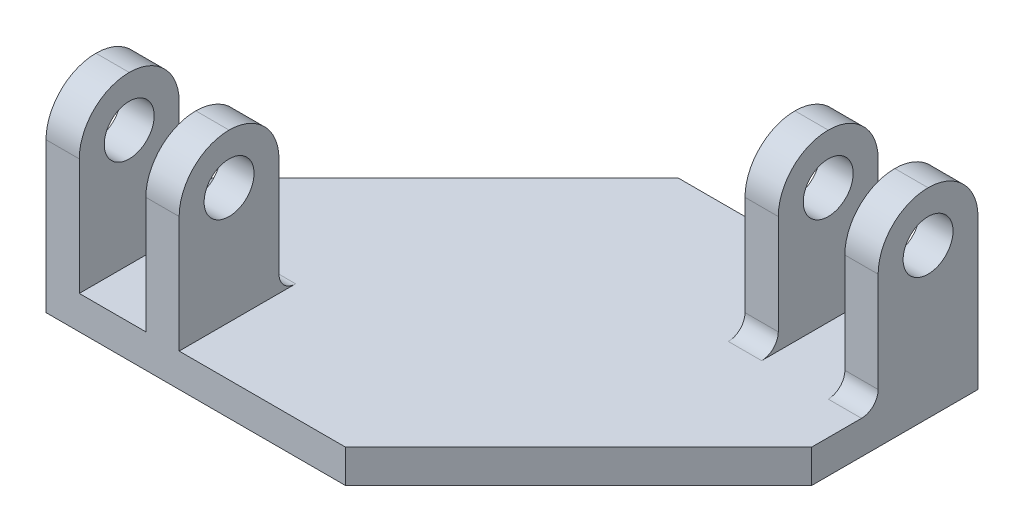
SolidWorks part; units mm, degrees
ref_plane "Front Plane" through (0, 0, 0) normal (0, 0, 1) x (1, 0, 0)
ref_plane "Top Plane" through (0, 0, 0) normal (0, 1, 0) x (1, 0, 0)
ref_plane "Right Plane" through (0, 0, 0) normal (1, 0, 0) x (0, 0, -1)
sketch "Sketch1" plane through (0, 0, 0) normal (0, 1, 0) x (1, 0, 0)
  line L1 (50.8, -38.1) -> (-50.8, -38.1)
  line L2 (50.8, -38.1) -> (50.8, 38.1)
  line L3 (50.8, 38.1) -> (-50.8, 38.1)
  line L4 (-50.8, -38.1) -> (-50.8, 38.1)
  line L5 (50.8, -38.1) -> (-50.8, 38.1) construction
  line L6 (50.8, 38.1) -> (-50.8, -38.1) construction
  point P0 (0, 0)
  dimension "D1" = 101.6
  dimension "D2" = 76.2
extrude "Boss-Extrude1" add sketch "Sketch1" along normal blind 6.35
sketch "Sketch2" plane through (0, 6.35, 0) normal (0, 1, 0) x (1, 0, 0)
  line L0 (-44.45, -19.05) -> (-44.45, -38.1)
  line L1 (-50.8, -38.1) -> (-25.4, -38.1)
  line L2 (-50.8, -38.1) -> (-50.8, -19.05)
  line L3 (-50.8, -19.05) -> (-25.4, -19.05)
  line L4 (-25.4, -38.1) -> (-25.4, -19.05)
  line L5 (50.8, 38.1) -> (25.4, 38.1)
  line L6 (50.8, 38.1) -> (50.8, 19.05)
  line L7 (50.8, 19.05) -> (25.4, 19.05)
  line L8 (25.4, 38.1) -> (25.4, 19.05)
  line L9 (31.75, 38.1) -> (31.75, 19.05)
  line L10 (-31.75, -19.05) -> (-31.75, -38.1)
  line L11 (44.45, 38.1) -> (44.45, 19.05)
  line M11 (-50.8, 38.1) -> (-50.8, -38.1)
  line M12 (-50.8, -38.1) -> (50.8, -38.1)
  line M13 (50.8, -38.1) -> (50.8, 38.1)
  line M14 (50.8, 38.1) -> (-50.8, 38.1)
  dimension "D1" = 25.4
  dimension "D2" = 19.05
  dimension "D3" = 6.35
  dimension "D4" = 6.35
  dimension "D5" = 6.35
  dimension "D6" = 6.35
extrude "Boss-Extrude2" add sketch "Sketch2" along normal blind 31.75 contours L3 L0 M11 M12 | L3 L10 L1 L4 | L9 L5 L8 L7 | L11 L7 M14 M13 region at (-47.625, 6.35, 28.575) region at (-28.575, 6.35, 28.575) region at (28.575, 6.35, -28.575) region at (47.625, 6.35, -28.575)
sketch "Sketch3" plane through (50.8, 0, 0) normal (1, 0, 0) x (0, 0, -1)
  line L0 (-28.575, 28.575) -> (28.575, 28.575) construction
  line L1 (28.575, 28.575) -> (38.1, 28.575) construction
  line L2 (38.1, 38.1) -> (38.1, 0) construction
  line L3 (-28.575, 28.575) -> (-38.1, 28.575) construction
  line L4 (-38.1, 38.1) -> (-38.1, 6.35) construction
  line L5 (19.05, 38.1) -> (38.1, 38.1) construction
  circle A0 centre (28.575, 28.575) radius 4.7625
  circle A1 centre (-28.575, 28.575) radius 4.7625
  dimension "D1" = 9.525
  dimension "D2" = 9.525
  dimension "D3" = 9.525
extrude "Cut-Extrude1" cut sketch "Sketch3" against normal through all
fillet "Fillet1" radius 3.175 4 edges at (47.625, 6.35, -19.05) (28.575, 6.35, -19.05) (-47.625, 6.35, 19.05) (-28.575, 6.35, 19.05)
fillet "Fillet2" radius 9.525 8 edges at (28.575, 38.1, -38.1) (47.625, 38.1, -38.1) (-47.625, 38.1, 38.1) (-28.575, 38.1, 38.1) (-47.625, 38.1, 19.05) (-28.575, 38.1, 19.05) (28.575, 38.1, -19.05) (47.625, 38.1, -19.05)
chamfer "Chamfer1" distance 44.45 angle 45 2 edges at (50.8, 3.175, 38.1) (-50.8, 3.175, -38.1)
